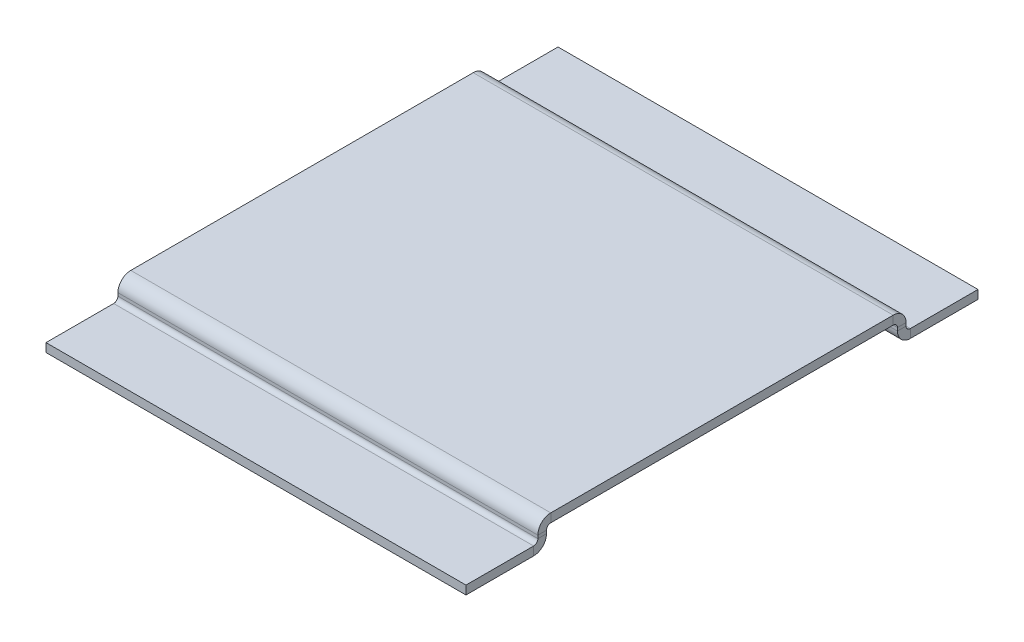
SolidWorks part; units mm, degrees
note: The reader was unsure of these and kept them because the rebuilt part matched: flange length of "Edge-Flange1", "Edge-Flange2".
ref_plane "Front Plane" through (0, 0, 0) normal (0, 0, 1) x (1, 0, 0)
ref_plane "Top Plane" through (0, 0, 0) normal (0, 1, 0) x (1, 0, 0)
ref_plane "Right Plane" through (0, 0, 0) normal (1, 0, 0) x (0, 0, -1)
sketch "Sketch1" plane through (0, 0, 0) normal (0, 1, 0) x (1, 0, 0)
  line L1 (36.5, -32) -> (-36.5, -32)
  line L2 (36.5, -32) -> (36.5, 32)
  line L3 (36.5, 32) -> (-36.5, 32)
  line L4 (-36.5, -32) -> (-36.5, 32)
  line L5 (36.5, -32) -> (-36.5, 32) construction
  line L6 (36.5, 32) -> (-36.5, -32) construction
  point P0 (0, 0)
  dimension "D1" = 73
  dimension "D2" = 64
base flange "Base-Flange1" sketch "Sketch1" thickness 1.5 reverse thickness direction no parameters "D1"=0.7366
edge flange "Edge-Flange1" sketch "Sketch10" flange profiles "Sketch10", "Sketch11" flange angle 90 flange length 5 flange position material inside bend radius 0.7366 thickness 1.5 relief rectangular parameters "D6"=10, "D8"=1
sketch "Sketch10" plane through (0, -1.5, 32) normal (0, 0, -1) x (1, 0, 0)
  line L2 (-36.5, 0) -> (-36.5, 3.5)
  line L3 (-36.5, 3.5) -> (36.5, 3.5)
  line L4 (36.5, 3.5) -> (36.5, 0)
  line L5 (36.5, 0) -> (-36.5, 0) construction
  line L6 (36.5, 0) -> (-36.5, 0)
sketch "Sketch11" plane through (0, -1.5, -32) normal (0, 0, 1) x (-1, 0, 0)
  line L0 (36.5, 0) -> (-36.5, 0) construction
  line L1 (36.5, 0) -> (-36.5, 0)
  line L2 (36.5, 0) -> (36.5, 3.5)
  line L3 (36.5, 3.5) -> (-36.5, 3.5)
  line L4 (-36.5, 3.5) -> (-36.5, 0)
bend "EdgeBend1" bend radius 0.7366 bend angle 90 parameters "D5"=1
bend "EdgeBend2" bend radius 0.7366 bend angle 90 parameters "D5"=2
edge flange "Edge-Flange2" sketch "Sketch16" flange profiles "Sketch16", "Sketch17" flange angle 90 flange length 14 flange position material inside bend radius 0.7366 thickness 1.5 relief rectangular parameters "D6"=10, "D8"=1
sketch "Sketch16" plane through (0, -5, 32) normal (0, -1, 0) x (1, 0, 0)
  line L2 (-36.5, 0) -> (-36.5, 12.5)
  line L3 (-36.5, 12.5) -> (36.5, 12.5)
  line L4 (36.5, 12.5) -> (36.5, 0)
  line L7 (36.5, 0) -> (-36.5, 0) construction
  line L8 (36.5, 0) -> (-36.5, 0)
sketch "Sketch17" plane through (0, -5, -32) normal (0, -1, 0) x (-1, 0, 0)
  line L0 (36.5, 0) -> (-36.5, 0) construction
  line L1 (36.5, 0) -> (-36.5, 0)
  line L2 (-36.5, 0) -> (-36.5, 12.5)
  line L3 (-36.5, 12.5) -> (36.5, 12.5)
  line L4 (36.5, 12.5) -> (36.5, 0)
bend "EdgeBend3" bend radius 0.7366 bend angle 90 parameters "D5"=3
bend "EdgeBend4" bend radius 0.7366 bend angle 90 parameters "D5"=4
sketch "Bend-Lines1" [suppressed] plane through (0, 0, 0) normal (0, 1, 0) x (1, 0, 0)
sketch "Bounding-Box1" [suppressed] plane through (0, 0, 0) normal (0, 1, 0) x (1, 0, 0)
sheet metal parameters "Sheet-Metal1" thickness 1.5 parameters "D1"=0.7366
flat pattern "Flat-Pattern1" [suppressed]
sketch "Bend-Lines2" plane through (0, 0, 0) normal (0, 1, 0) x (1, 0, 0)
sketch3d "Bounding-Box2" [suppressed]
  line L0 (-36.5, -32, 0) -> (36.5, -32, 0) construction
  line L1 (-36.5, 32, 0) -> (36.5, 32, 0) construction
  line L2 (-36.5, -32, 0) -> (-36.5, 32, 0) construction
  line L3 (36.5, -32, 0) -> (36.5, 32, 0) construction
sheet metal parameters "Sheet-Metal2" thickness 1.5 parameters "D1"=0.7366
flat pattern "Flat-Pattern1"
sketch "Bend-Lines2" plane through (0, 0, 0) normal (0, 1, 0) x (1, 0, 0)
  line L0 (36.5, 30.931) -> (-36.5, 30.931) construction
  line L1 (-36.5, -30.931) -> (36.5, -30.931) construction
  line L2 (36.5, 30.931) -> (-36.5, 30.931) construction
  line L3 (-36.5, -30.931) -> (36.5, -30.931) construction
sketch3d "Bounding-Box2" [suppressed]
  line L0 (36.5, -34.8619, 0) -> (-36.5, -34.8619, 0) construction
  line L1 (36.5, 34.8619, 0) -> (-36.5, 34.8619, 0) construction
  line L2 (36.5, -34.8619, 0) -> (36.5, 34.8619, 0) construction
  line L3 (-36.5, -34.8619, 0) -> (-36.5, 34.8619, 0) construction
bend of the flat pattern "Flatten-<EdgeBend1>1"
bend of the flat pattern "Flatten-<EdgeBend2>1"
sheet metal parameters "Sheet-Metal3" thickness 1.5 parameters "D1"=0.7366
flat pattern "Flat-Pattern1"
sketch "Bend-Lines2" plane through (0, 0, 0) normal (0, 1, 0) x (1, 0, 0)
  line L0 (36.5, 30.931) -> (-36.5, 30.931) construction
  line L1 (-36.5, -30.931) -> (36.5, -30.931) construction
  line L2 (36.5, 30.931) -> (-36.5, 30.931) construction
  line L3 (-36.5, -30.931) -> (36.5, -30.931) construction
  line L4 (36.5, 33.7929) -> (-36.5, 33.7929) construction
  line L5 (-36.5, -33.7929) -> (36.5, -33.7929) construction
  line L6 (36.5, 33.7929) -> (-36.5, 33.7929) construction
  line L7 (-36.5, -33.7929) -> (36.5, -33.7929) construction
sketch3d "Bounding-Box2" [suppressed]
  line L0 (-36.5, 46.7239, 0) -> (-36.5, -46.7239, 0) construction
  line L1 (36.5, 46.7239, 0) -> (36.5, -46.7239, 0) construction
  line L2 (-36.5, 46.7239, 0) -> (36.5, 46.7239, 0) construction
  line L3 (-36.5, -46.7239, 0) -> (36.5, -46.7239, 0) construction
bend of the flat pattern "Flatten-<EdgeBend1>1"
bend of the flat pattern "Flatten-<EdgeBend2>1"
bend of the flat pattern "Flatten-<EdgeBend3>1"
bend of the flat pattern "Flatten-<EdgeBend4>1"
